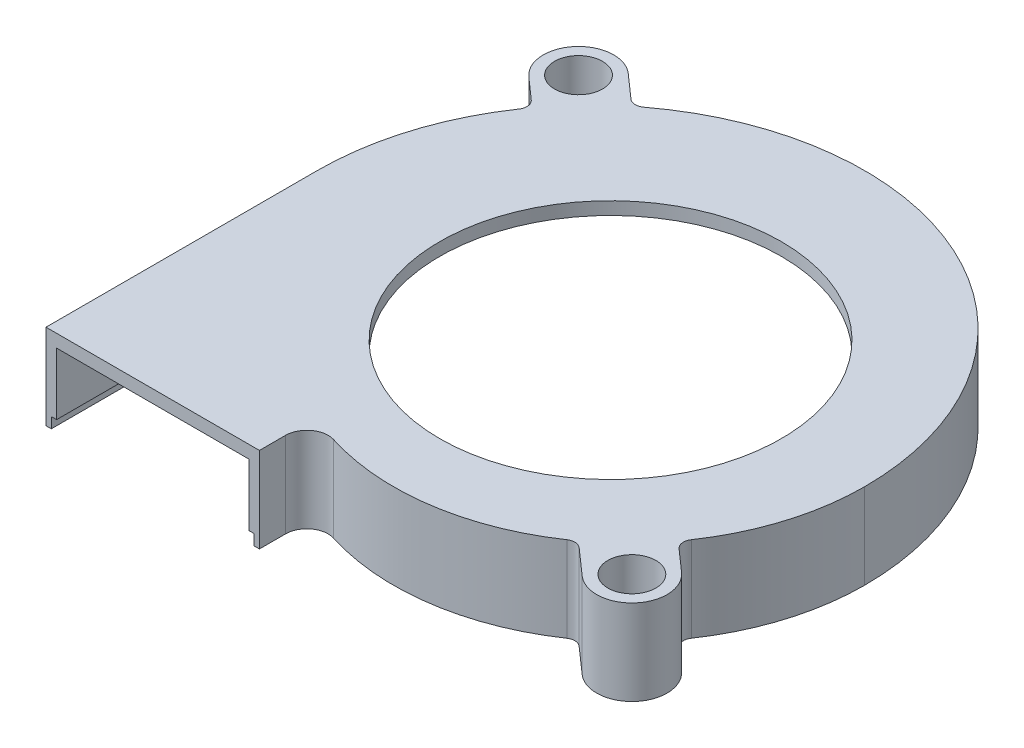
SolidWorks part; units mm, degrees
material "PET"
ref_plane "Спереди" through (0, 0, 0) normal (0, 0, 1) x (1, 0, 0)
ref_plane "Сверху" through (0, 0, 0) normal (0, 1, 0) x (1, 0, 0)
ref_plane "Справа" through (0, 0, 0) normal (1, 0, 0) x (0, 0, -1)
sketch "Эскиз1" plane through (0, 0, 0) normal (0, 1, 0) x (1, 0, 0)
  line L0 (0, -37.0288) -> (0, 52.769) construction
  line L1 (-41.2177, 0) -> (28.9689, 0) construction
  line L2 (-27.5, -25.4) -> (-7.5, -25.4)
  line L3 (-7.5, -25.4) -> (-7.5, -22.9558)
  line L4 (-27.5, -25.4) -> (-27.5, 0)
  line L5 (17.8147, -20.4728) -> (22.1853, -15.5272) construction
  line L6 (-25.1853, 17.5272) -> (-20.8147, 22.4728) construction
  line L7 (-23, 20) -> (20, -18) construction
  line L8 (-20.8147, 22.4728) -> (-18.5989, 20.5146)
  line L9 (-25.1853, 17.5272) -> (-23.2069, 15.7789)
  line L10 (17.8147, -20.4728) -> (15.377, -18.3185)
  line L11 (22.1853, -15.5272) -> (20.1437, -13.7231)
  circle A0 centre (0, 0) radius 16
  arc A1 (23.8, 0) -> (-17.3331, 20.4667) centre (-1.85, 0.0168) ccw
  circle A2 centre (-23, 20) radius 2.25
  circle A3 centre (20, -18) radius 2.25
  arc A4 (23.8, 0) -> (19.9791, -12.4113) centre (1.7319, 0) cw
  arc A5 (22.1853, -15.5272) -> (17.8147, -20.4728) centre (20, -18) cw
  arc A6 (-25.1853, 17.5272) -> (-20.8147, 22.4728) centre (-23, 20) cw
  arc A7 (14.152, -18.2412) -> (-4.899, -21.0483) centre (1.7319, 0) cw
  arc A8 (-23.0428, 14.4662) -> (-27.5, 0) centre (-1.85, 0.0168) ccw
  arc A9 (-4.899, -21.0483) -> (-7.5, -22.9558) centre (-5.5, -22.9558) ccw
  arc A10 (-18.5989, 20.5146) -> (-17.3331, 20.4667) centre (-17.9367, 21.2639) ccw
  arc A11 (-23.2069, 15.7789) -> (-23.0428, 14.4662) centre (-23.8691, 15.0296) cw
  arc A12 (20.1437, -13.7231) -> (19.9791, -12.4113) centre (20.8059, -12.9738) cw
  arc A13 (15.377, -18.3185) -> (14.152, -18.2412) centre (14.7148, -19.0678) ccw
  point P14 (0, 25.6)
  point P16 (16, 0)
  point P17 (0, -22)
  point P20 (23.8, 0)
  point P26 (0, -16)
  point P34 (-22.5346, 15.1848)
  point P41 (14.784, -17.7945)
  dimension "D1" = 18
  dimension "D2" = 20
  dimension "D8" = 51
  dimension "D11" = 3.3
  dimension "D12" = 7.8
  dimension "D13" = 6
  dimension "D14" = 2
  dimension "D5" = 4.5
  dimension "D6" = 32
  dimension "D15" = 1
  dimension "D3" = 23
  dimension "D4" = 20
  dimension "D7" = 51.3
  dimension "D9" = 20
  dimension "D10" = 25.4
extrude "Бобышка-Вытянуть1" add sketch "Эскиз1" against normal blind 8
sketch "Эскиз2" plane through (0, -8, 0) normal (0, -1, 0) x (-1, 0, 0)
  line L12 (7.5, -25.4) -> (7.5, -22.9558) construction
  line L13 (27.5, 0) -> (27.5, -25.4) construction
  line L14 (7.5, -25.4) -> (7.5, -22.9558) construction
  line L15 (27.5, 0) -> (27.5, -25.4) construction
  line L16 (8.5, -25.4) -> (8.5, -22.9558)
  line L17 (26.5, 0.0003) -> (26.5, -25.4)
  line L18 (26.5, -25.4) -> (8.5, -25.4)
  arc A19 (17.3331, 20.4667) -> (-23.8, 0) centre (1.85, 0.0168) ccw construction
  arc A20 (-23.8, 0) -> (-19.9791, -12.4113) centre (-1.7319, 0) ccw construction
  arc A21 (-14.152, -18.2412) -> (4.899, -21.0483) centre (-1.7319, 0) ccw construction
  arc A22 (7.5, -22.9558) -> (4.899, -21.0483) centre (5.5, -22.9558) ccw construction
  arc A23 (27.5, 0) -> (23.0428, 14.4662) centre (1.85, 0.0168) ccw construction
  arc A24 (17.3331, 20.4667) -> (-23.8, 0) centre (1.85, 0.0168) ccw construction
  arc A25 (-23.8, 0) -> (-19.9791, -12.4113) centre (-1.7319, 0) ccw construction
  arc A26 (-14.152, -18.2412) -> (4.899, -21.0483) centre (-1.7319, 0) ccw construction
  arc A27 (7.5, -22.9558) -> (4.899, -21.0483) centre (5.5, -22.9558) ccw construction
  arc A28 (27.5, 0) -> (23.0428, 14.4662) centre (1.85, 0.0168) ccw construction
  arc A29 (17.3331, 20.4667) -> (23.0428, 14.4662) centre (1.85, 0.0168) cw construction
  arc A30 (-19.9791, -12.4113) -> (-14.152, -18.2412) centre (-1.7319, 0) ccw construction
  arc A31 (8.5, -22.9558) -> (4.5986, -20.0945) centre (5.5, -22.9558) ccw
  arc A32 (-13.5892, -17.4146) -> (4.5986, -20.0945) centre (-1.7319, 0) ccw
  arc A33 (-19.1522, -11.8489) -> (-13.5892, -17.4146) centre (-1.7319, 0) ccw
  arc A34 (-22.8, 0.0003) -> (-19.1522, -11.8489) centre (-1.7319, 0) ccw
  arc A35 (16.7295, 19.6694) -> (-22.8, 0.0003) centre (1.85, 0.0168) ccw
  arc A36 (16.7295, 19.6694) -> (22.2166, 13.9029) centre (1.85, 0.0168) cw
  arc A37 (26.5, 0.0003) -> (22.2166, 13.9029) centre (1.85, 0.0168) ccw
  dimension "D1" = 1
extrude "Вырез-Вытянуть1" cut sketch "Эскиз2" against normal offset from surface (6.8 mm away) 1.2 up to face at (0, 0, 16)
sketch "Эскиз11" plane through (0, -8, 0) normal (0, -1, 0) x (1, 0, 0)
  line L0 (-8.5, 22.9558) -> (-8.5, 25.4) construction
  line L1 (-26.5, 25.4) -> (-26.5, -0.0003) construction
  line L2 (-8.5, 22.9558) -> (-8.5, 25.4)
  line L3 (-26.5, 25.4) -> (-26.5, -0.0003)
  line L4 (-27, 25.4) -> (-27, -0.0002)
  line L5 (-8, 22.9558) -> (-8, 25.4)
  line L6 (-27, 25.4) -> (-26.5, 25.4)
  line L7 (-8.5, 25.4) -> (-8, 25.4)
  arc A0 (-8.5, 22.9558) -> (-4.5986, 20.0945) centre (-5.5, 22.9558) ccw construction
  arc A1 (22.8, -0.0003) -> (-4.5986, 20.0945) centre (1.7319, 0) ccw construction
  arc A2 (-26.5, -0.0003) -> (22.8, -0.0003) centre (-1.85, -0.0168) ccw construction
  arc A3 (-8.5, 22.9558) -> (-4.5986, 20.0945) centre (-5.5, 22.9558) ccw
  arc A4 (22.8, -0.0003) -> (-4.5986, 20.0945) centre (1.7319, 0) ccw
  arc A5 (-26.5, -0.0003) -> (22.8, -0.0003) centre (-1.85, -0.0168) ccw
  arc A6 (-27, -0.0002) -> (23.3, -0.0001) centre (-1.85, -0.0168) ccw
  arc A7 (23.3, -0.0001) -> (-4.7488, 20.5714) centre (1.7319, 0) ccw
  arc A8 (-8, 22.9558) -> (-4.7488, 20.5714) centre (-5.5, 22.9558) ccw
  dimension "D1" = 0.5
extrude "Вырез-Вытянуть8" cut sketch "Эскиз11" against normal blind 1
sketch "Sketch1" plane through (0, 0, 25.4) normal (0, 0, 1) x (1, 0, 0)
  line L0 (-17.5, -1.2) -> (-17.5, -8) construction
  line L1 (-26.5, -1.2) -> (-8.5, -1.2) construction
  line L2 (-27, -8) -> (23.3, -8) construction
